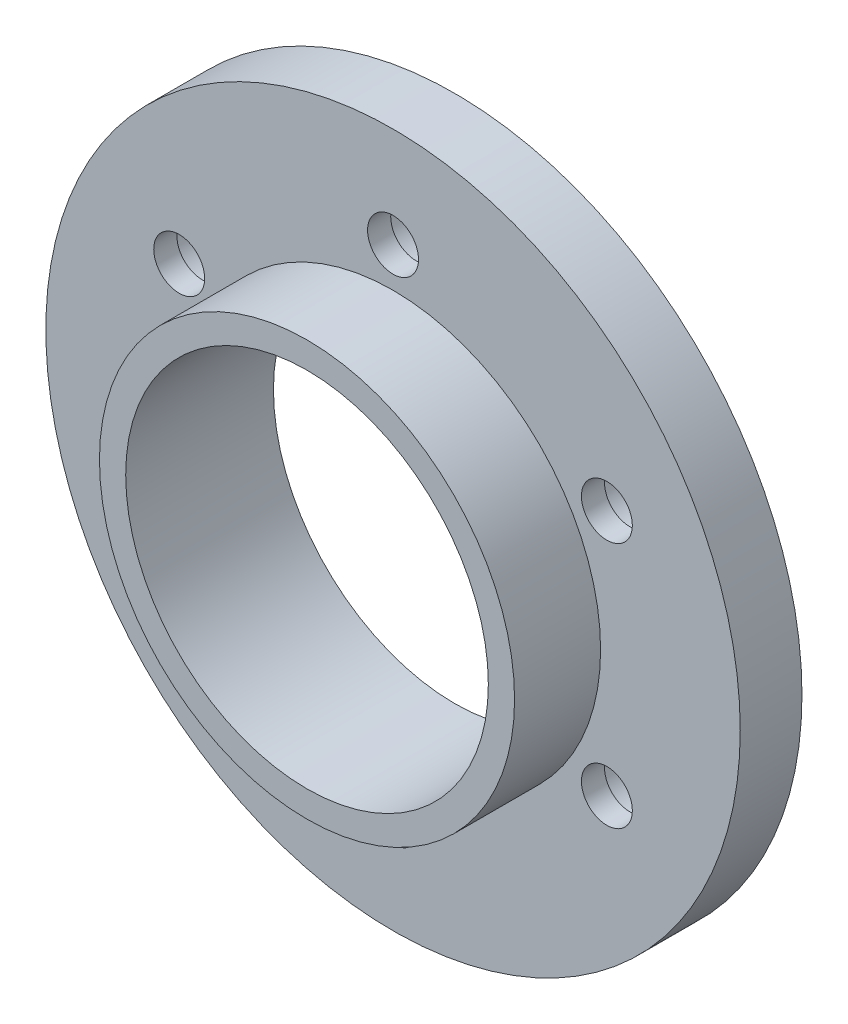
SolidWorks part; units mm, degrees
material "Stainless Steel (ferritic)"
ref_plane "Front Plane" through (0, 0, 0) normal (0, 0, 1) x (1, 0, 0)
ref_plane "Top Plane" through (0, 0, 0) normal (0, 1, 0) x (1, 0, 0)
ref_plane "Right Plane" through (0, 0, 0) normal (1, 0, 0) x (0, 0, -1)
sketch "Sketch2" plane through (0, 0, 0) normal (0, 0, 1) x (1, 0, 0)
  circle A0 centre (0, 0) radius 45
  dimension "D1" = 90
extrude "Boss-Extrude1" add sketch "Sketch2" along normal blind 8
sketch "Sketch5" plane through (0, 0, 8) normal (0, 0, 1) x (1, 0, 0)
  circle A0 centre (0, 0) radius 23.5
  dimension "D1" = 47
extrude "Cut-Extrude1" cut sketch "Sketch5" against normal through all
sketch "Sketch6" plane through (0, 0, 8) normal (0, 0, 1) x (1, 0, 0)
  circle A1 centre (0, 0) radius 26.9
  dimension "D1" = 53.8
extrude "Boss-Extrude2" add sketch "Sketch6" along normal blind 11.148
sketch "Sketch7" plane through (0, 0, 19.148) normal (0, 0, 1) x (1, 0, 0)
  circle A0 centre (0, 0) radius 23.5
  dimension "D1" = 47
extrude "Cut-Extrude3" cut sketch "Sketch7" against normal through all
sketch "Sketch8" plane through (0, 0, 0) normal (0, 0, -1) x (-1, 0, 0)
  line L0 (0, 0) -> (0, 32) construction
  dimension "D1" = 32
hole_wizard "CBORE for M8 Hex Head Bolt1" positions "3DSketch1" profile "Sketch9" counterbore size "M8" standard "ANSI Metric" end condition through all
sketch3d "3DSketch1"
  point P0 (0, 32, 0)
sketch "Sketch9" plane through (0, 32, 0) normal (1, 0, 0) x (0, 1, 0)
  line L0 (0, 0) -> (0, 19.148)
  line L1 (0, 19.148) -> (3.3, 19.148)
  line L3 (3.3, 19.148) -> (3.3, 5)
  line L4 (3.3, 5) -> (5, 5)
  line L5 (5, 5) -> (5, 0)
  line L7 (5, 0) -> (0, 0)
  line L11 (0, -6.35) -> (0, 107.95) construction
  dimension "Thru Hole Dia." = 6.6
  dimension "Thru Hole Depth" = 19.148
  dimension "C'Bore Dia." = 10
  dimension "C'Bore Depth" = 5
pattern_circular "CirPattern1" count 6 over 360 about axis through (0, 0, 0) along (0, 0, 1) of "CBORE for M8 Hex Head Bolt1"
